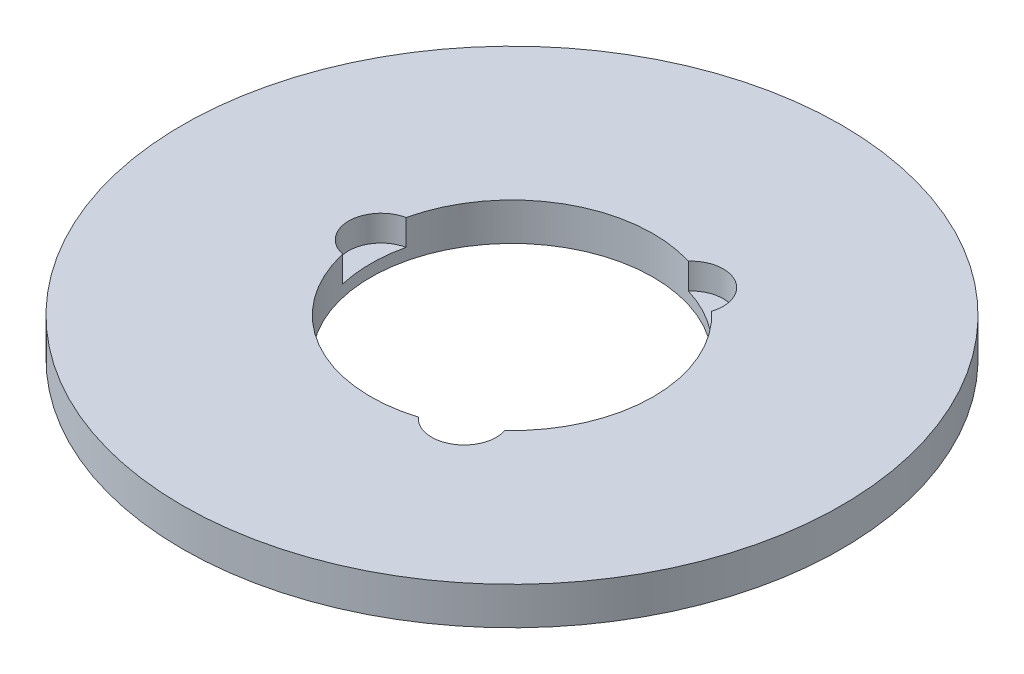
SolidWorks part; units mm, degrees
ref_plane "Front Plane" through (0, 0, 0) normal (0, 0, 1) x (1, 0, 0)
ref_plane "Top Plane" through (0, 0, 0) normal (0, 1, 0) x (1, 0, 0)
ref_plane "Right Plane" through (0, 0, 0) normal (1, 0, 0) x (0, 0, -1)
sketch "Sketch1" plane through (0, 0, 0) normal (0, 1, 0) x (1, 0, 0)
  circle A0 centre (0, 0) radius 70
  dimension "FLANGE_OD" = 140
extrude "Boss-Extrude1" add sketch "Sketch1" along normal blind 8
sketch "Sketch2" plane through (0, 0, 0) normal (0, 1, 0) x (1, 0, 0)
  circle A0 centre (0, 0) radius 30
  dimension "BORE_D" = 60
extrude "Cut-Extrude1" cut sketch "Sketch2" along normal through all
sketch "Sketch3" plane through (0, 8, 0) normal (0, 1, 0) x (1, 0, 0)
  circle A0 centre (0, 0) radius 27.809 construction
  circle A1 centre (-27.809, 0) radius 6.8885
  dimension "BOLT_D" = 13.777
  dimension "BOLT_PCD" = 55.6181
extrude "Cut-Extrude2" cut sketch "Sketch3" against normal blind 5.49
pattern_circular "CirPattern1" count 3 over 360 about axis through (0, 0, 0) along (0, 1, 0) of "Cut-Extrude2"
